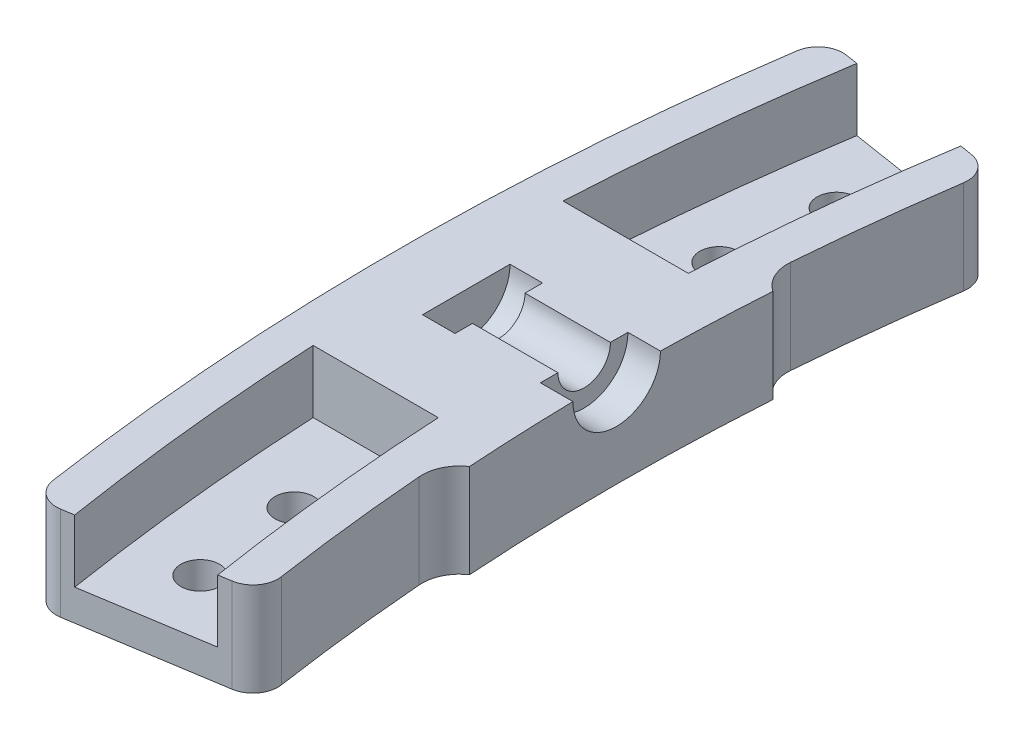
SolidWorks part; units mm, degrees
ref_plane "Front Plane" through (0, 0, 0) normal (0, 0, 1) x (1, 0, 0)
ref_plane "Top Plane" through (0, 0, 0) normal (0, 1, 0) x (1, 0, 0)
ref_plane "Right Plane" through (0, 0, 0) normal (1, 0, 0) x (0, 0, -1)
sketch "Sketch1" plane through (0, 0, 0) normal (0, 1, 0) x (1, 0, 0)
  line L0 (0, 0) -> (-197.5377, -31.2869) construction
  line L1 (0, 0) -> (-197.5377, 31.2869) construction
  line L2 (0, 0) -> (-195, 0) construction
  line L3 (-197.5377, 31.2869) -> (-187.6608, 29.7225)
  line L4 (-187.6608, -29.7225) -> (-197.5377, -31.2869)
  line L5 (0, 0) -> (-200.5007, -31.7562) construction
  line L6 (0, 0) -> (-200.5007, 31.7562) construction
  line L7 (-200.5007, 31.7562) -> (-184.6977, 29.2532)
  line L8 (-200.5007, -31.7562) -> (-184.6977, -29.2532)
  arc A0 (-197.5377, 31.2869) -> (-197.5377, -31.2869) centre (0, 0) ccw
  arc A1 (-187.6608, 29.7225) -> (-187.6608, -29.7225) centre (0, 0) ccw
  arc A2 (-192.5992, -30.5047) -> (-192.5992, 30.5047) centre (0, 0) cw construction
  arc A4 (-184.6977, 29.2532) -> (-184.6977, -29.2532) centre (0, 0) ccw
  arc A5 (-200.5007, 31.7562) -> (-200.5007, -31.7562) centre (0, 0) ccw
  dimension "D1" = 200
  dimension "D2" = 190
  dimension "D3" = 5
  dimension "D5" = 187
  dimension "D6" = 203
  dimension "D4" = 18
extrude "Boss-Extrude1" add sketch "Sketch1" along normal blind 10 contours A1 L3 A0 L4 | L7 A5 L8 A0 | A4 L7 A1 L8 region at (-200.6761, 0, 0) region at (-194.2416, 0, 0) region at (-187.7297, 0, 0)
ref_plane "Plane1" through (-195, 0, 0) normal (1, 0, 0) x (0, 0, -1)
sketch "Sketch15" plane through (0, 10, 0) normal (0, 1, 0) x (1, 0, 0)
  line L0 (-187.6608, -29.7225) -> (-197.5377, -31.2869) construction
  line L1 (-185, 10) -> (-205, 10)
  line L2 (-185, 10) -> (-185, -10)
  line L3 (-185, -10) -> (-205, -10)
  line L4 (-205, 10) -> (-205, -10)
  line L5 (-185, 10) -> (-205, -10) construction
  line L6 (-185, -10) -> (-205, 10) construction
  line L7 (-197.5377, 31.2869) -> (-187.6608, 29.7225) construction
  line L8 (-187.6608, -29.7225) -> (-197.5377, -31.2869)
  line L9 (-197.5377, 31.2869) -> (-187.6608, 29.7225)
  arc A2 (-187.6608, 29.7225) -> (-187.6608, -29.7225) centre (0, 0) ccw construction
  arc A3 (-197.5377, 31.2869) -> (-197.5377, -31.2869) centre (0, 0) ccw construction
  arc A4 (-187.6608, 29.7225) -> (-187.6608, -29.7225) centre (0, 0) ccw
  arc A5 (-197.5377, 31.2869) -> (-197.5377, -31.2869) centre (0, 0) ccw
  point P0 (-195, 0)
  line M5 (-200.5007, -31.7562) -> (-184.6977, -29.2532)
  line M7 (-184.6977, 29.2532) -> (-200.5007, 31.7562)
  dimension "D1" = 20
  dimension "D2" = 20
extrude "Cut-Extrude1" cut sketch "Sketch15" against normal blind 5 contours A5 L1 A4 M7 | L3 A5 A4 M5 region at (-193.9153, 10, -20.2762) region at (-193.9153, 10, 20.2762)
ref_plane "Plane2" through (-195, 0, 0) normal (-1, 0, 0) x (0, 0, 1)
sketch "Sketch12" plane through (0, 0, 0) normal (0, 1, 0) x (1, 0, 0)
  line L0 (0, 0) -> (-194.258, -16.9954) construction
  line L1 (0, 0) -> (-193.3317, -25.4526) construction
  line L2 (0, 0) -> (-195, 0) construction
  line L3 (0, 0) -> (-195, 0) construction
  line L4 (0, 0) -> (-194.258, 16.9954) construction
  line L5 (0, 0) -> (-193.3317, 25.4526) construction
  arc A0 (-192.5992, 30.5047) -> (-192.5992, -30.5047) centre (0, 0) ccw construction
  dimension "D1" = 10
  dimension "D2" = 15
hole_wizard "Ø3.1 (3.1) Diameter Hole2" positions "Sketch18" profile "Sketch17" hole size "Ø3.1" standard "ISO" end condition through all
sketch "Sketch18" plane through (0, 0, 0) normal (0, -1, 0) x (-1, 0, 0)
  point P0 (193.3317, -25.4526)
  point P3 (194.258, -16.9954)
  point P6 (194.258, 16.9954)
  point P9 (193.3317, 25.4526)
sketch "Sketch17" plane through (-193.3317, 0, 25.4526) normal (1, 0, 0) x (0, 0, -1)
  line L0 (0, 0) -> (0, 10)
  line L1 (0, 10) -> (1.55, 10)
  line L2 (1.55, 10) -> (1.55, 0)
  line L5 (1.55, 0) -> (0, 0)
  line L11 (0, -6.35) -> (0, 107.95) construction
  dimension "Thru Hole Dia." = 3.1
  dimension "Thru Hole Depth" = 10
sketch "Sketch19" plane through (0, 0, 0) normal (0, 1, 0) x (1, 0, 0)
  line L0 (0, 0) -> (-185.1028, -12.1323) construction
  line L1 (0, 0) -> (-185.5, 0) construction
  line L2 (-185.1028, -12.1323) -> (-186.5996, -12.2304)
  line L3 (-185.1028, 12.1323) -> (-186.5996, 12.2304)
  arc A0 (-185.1028, 12.1323) -> (-185.1028, -12.1323) centre (0, 0) ccw
  arc A1 (-184.6977, 29.2532) -> (-184.6977, -29.2532) centre (0, 0) ccw construction
  arc A2 (-186.5996, 12.2304) -> (-186.5996, -12.2304) centre (0, 0) ccw
  dimension "D1" = 185.5
  dimension "D2" = 3.75
extrude "Boss-Extrude2" add sketch "Sketch19" along normal blind 10
fillet "Fillet1" radius 3 2 edges at (-186.5996, 5, -12.2304) (-186.5996, 5, 12.2304)
fillet "Fillet2" radius 2 4 edges at (-200.5007, 5, -31.7562) (-200.5007, 5, 31.7562) (-184.6977, 5, 29.2532) (-184.6977, 5, -29.2532)
sketch "Sketch20" plane through (0, 10, 0) normal (0, 1, 0) x (1, 0, 0)
  line L0 (0, 0) -> (-185, 0) construction
  line L1 (-185, 0) -> (-197.5, 0) construction
  dimension "D1" = 185
  dimension "D2" = 12.5
ref_plane "Plane3" through (-197.5, 0, 0) normal (1, 0, 0) x (0, 0, -1)
sketch "Sketch21" plane through (-197.5, 0, 0) normal (1, 0, 0) x (0, 0, -1)
  line L0 (12.1323, 10) -> (-12.1323, 10) construction
  circle A0 centre (0, 10) radius 2.1
  dimension "D1" = 4.2
extrude "Cut-Extrude2" cut sketch "Sketch21" along normal through all
sketch "Sketch22" plane through (-197.5, 0, 0) normal (1, 0, 0) x (0, 0, -1)
  line L0 (-2.1, 10) -> (2.1, 10) construction
  circle A0 centre (0, 10) radius 3.5
  dimension "D1" = 7
extrude "Cut-Extrude3" cut sketch "Sketch22" along normal blind 2.6
sketch "Sketch23" plane through (-197.5, 0, 0) normal (1, 0, 0) x (0, 0, -1)
  line L0 (-3.5, 10) -> (3.5, 10) construction
  circle A0 centre (0, 10) radius 2.5
  dimension "D1" = 5
extrude "Cut-Extrude4" [suppressed] cut sketch "Sketch23" against normal blind 0.2 and the other way blind 2.7
sketch "Sketch24" [suppressed] plane through (0, 10, 0) normal (0, 1, 0) x (1, 0, 0)
  line L0 (-185.5, 0) -> (-197.5, 0) construction
  line L2 (-197.5, -2.5) -> (-197.5, 2.5) construction
  line L3 (-188.067, 0) -> (-185.467, 0)
  line L4 (-188.067, 0) -> (-188.067, 3.5)
  line L5 (-188.067, 3.5) -> (-185.467, 3.5)
  line L6 (-185.467, 0) -> (-185.467, 3.5)
  arc A0 (-185.4881, 2.1) -> (-185.4881, -2.1) centre (0, 0) ccw construction
  arc A1 (-185.1028, 12.1323) -> (-185.4881, 2.1) centre (0, 0) ccw construction
  point P5 (-197.5, 0)
  dimension "D1" = 2.6
  dimension "D2" = 7
revolve "Cut-Revolve1" [suppressed] cut sketch "Sketch24" angle 360 about L0
sketch "Sketch25" [suppressed] plane through (-188.067, 0, 0) normal (1, 0, 0) x (0, 0, -1)
  line L0 (-2.5, 10) -> (2.5, 10) construction
  circle A0 centre (0, 10) radius 2.5
  dimension "D1" = 5
extrude "Cut-Extrude5" [suppressed] cut sketch "Sketch25" against normal up to surface (9.633 mm away) up to face at (-197.5, 8.25, 0)
sketch "Sketch26" plane through (0, 0, 0) normal (0, -1, 0) x (1, 0, 0)
  line L2 (-198.5155, -31.4418) -> (-186.6626, -29.5645)
  line L3 (-186.6626, 29.5645) -> (-198.5155, 31.4418)
  line L4 (-198.5155, -31.4418) -> (-186.6626, -29.5645)
  line L5 (-186.6626, 29.5645) -> (-198.5155, 31.4418)
  arc A10 (-200.8068, 29.7596) -> (-200.8068, -29.7596) centre (0, 0) ccw
  arc A11 (-200.8068, -29.7596) -> (-198.5155, -31.4418) centre (-198.8284, -29.4664) ccw
  arc A12 (-186.6626, -29.5645) -> (-184.9969, -27.2971) centre (-186.9755, -27.5891) ccw
  arc A13 (-186.4092, -14.8532) -> (-184.9969, -27.2971) centre (0, 0) ccw
  arc A14 (-185.1028, -12.1323) -> (-186.4092, -14.8532) centre (-183.4187, -14.6149) ccw
  arc A15 (-185.1028, 12.1323) -> (-185.1028, -12.1323) centre (0, 0) ccw
  arc A16 (-186.4092, 14.8532) -> (-185.1028, 12.1323) centre (-183.4187, 14.6149) ccw
  arc A17 (-184.9969, 27.2971) -> (-186.4092, 14.8532) centre (0, 0) ccw
  arc A18 (-184.9969, 27.2971) -> (-186.6626, 29.5645) centre (-186.9755, 27.5891) ccw
  arc A19 (-198.5155, 31.4418) -> (-200.8068, 29.7596) centre (-198.8284, 29.4664) ccw
  arc A20 (-200.8068, 29.7596) -> (-200.8068, -29.7596) centre (0, 0) ccw
  arc A21 (-200.8068, -29.7596) -> (-198.5155, -31.4418) centre (-198.8284, -29.4664) ccw
  arc A22 (-186.6626, -29.5645) -> (-184.9969, -27.2971) centre (-186.9755, -27.5891) ccw
  arc A23 (-186.4092, -14.8532) -> (-184.9969, -27.2971) centre (0, 0) ccw
  arc A24 (-185.1028, -12.1323) -> (-186.4092, -14.8532) centre (-183.4187, -14.6149) ccw
  arc A25 (-185.1028, 12.1323) -> (-185.1028, -12.1323) centre (0, 0) ccw
  arc A26 (-186.4092, 14.8532) -> (-185.1028, 12.1323) centre (-183.4187, 14.6149) ccw
  arc A27 (-184.9969, 27.2971) -> (-186.4092, 14.8532) centre (0, 0) ccw
  arc A28 (-184.9969, 27.2971) -> (-186.6626, 29.5645) centre (-186.9755, 27.5891) ccw
  arc A29 (-198.5155, 31.4418) -> (-200.8068, 29.7596) centre (-198.8284, 29.4664) ccw
  dimension "D1" = 0
extrude "Cut-Extrude6" cut sketch "Sketch26" against normal blind 2.5
sketch "Sketch27" plane through (0, 10, 0) normal (0, 1, 0) x (1, 0, 0)
  line L0 (-197.5, 0) -> (-185.467, 0) construction
  line L1 (-197.5, -3.5) -> (-197.5, 3.5) construction
  line L3 (-188.067, 3.5) -> (-185.467, 3.5)
  line L4 (-188.067, 3.5) -> (-188.067, 0)
  line L5 (-188.067, 0) -> (-185.467, 0)
  line L6 (-185.467, 3.5) -> (-185.467, 0)
  arc A1 (-185.1028, 12.1323) -> (-185.4881, 2.1) centre (0, 0) ccw construction
  point P4 (-185.467, 3.5)
  dimension "D1" = 2.6
  dimension "D2" = 7
revolve "Cut-Revolve3" cut sketch "Sketch27" angle 360 about L0
